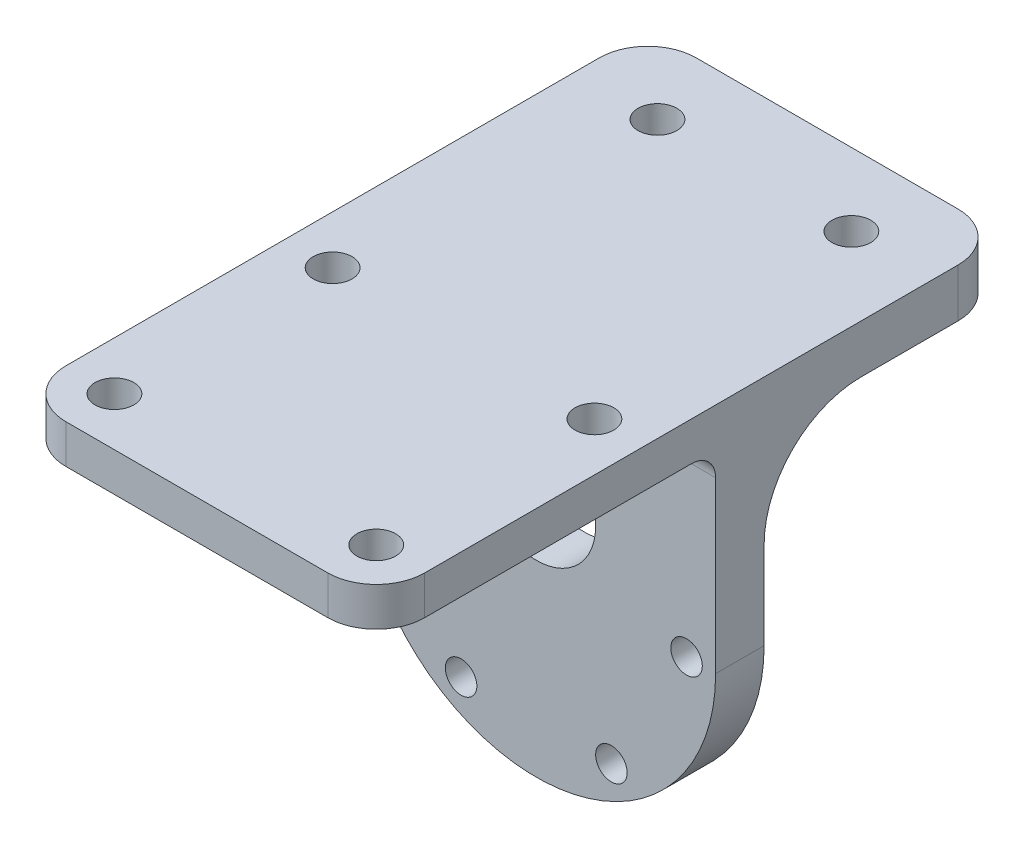
SolidWorks part; units mm, degrees
material "PMMA"
ref_plane "Front Plane" through (0, 0, 0) normal (0, 0, 1) x (1, 0, 0)
ref_plane "Top Plane" through (0, 0, 0) normal (0, 1, 0) x (1, 0, 0)
ref_plane "Right Plane" through (0, 0, 0) normal (1, 0, 0) x (0, 0, -1)
sketch "Sketch1" plane through (0, 0, 0) normal (0, 0, 1) x (1, 0, 0)
  line L0 (-18.5, 0) -> (18.5, 0) construction
  line L1 (0, 18.5) -> (0, -18.5) construction
  line L4 (-18.5, 0) -> (-18.5, 20)
  line L5 (-18.5, 20) -> (18.5, 20)
  line L6 (18.5, 0) -> (18.5, 20)
  arc A0 (-18.5, 0) -> (18.5, 0) centre (0, 0) ccw
  circle A1 centre (-15.5, 0) radius 1.625
  circle A2 centre (-7.75, 13.4234) radius 1.625 construction
  circle A3 centre (7.75, 13.4234) radius 1.625 construction
  circle A4 centre (15.5, 0) radius 1.625
  circle A5 centre (7.75, -13.4234) radius 1.625
  circle A6 centre (-7.75, -13.4234) radius 1.625
  circle A7 centre (0, 7) radius 6.125
  point P21 (0, 0)
  dimension "D1" = 37
  dimension "D2" = 3.25
  dimension "D6" = 12.25
  dimension "D3" = 15.5
  dimension "D5" = 7
  dimension "D7" = 15.5
  dimension "D8" = 20
  dimension "D4" = 6
extrude "Boss-Extrude2" add sketch "Sketch1" along normal blind 5 contours L4 A0 L6 L5 A7 A6 A5 A4 A3 A2 A1 region at (-17.966, 10, 0)
sketch "Sketch7" plane through (0, 0, 0) normal (0, 0, -1) x (-1, 0, 0)
  line L1 (-18.5, 20) -> (18.5, 20)
  line L2 (-18.5, 20) -> (-18.5, 24)
  line L3 (-18.5, 24) -> (18.5, 24)
  line L4 (18.5, 20) -> (18.5, 24)
  dimension "D1" = 4
extrude "Boss-Extrude7" add sketch "Sketch7" against normal blind 40
fillet "Fillet3" radius 2.5 1 edges at (0, 20, 5)
sketch "Sketch10" plane through (0, 0, 0) normal (0, 0, -1) x (-1, 0, 0)
  line L0 (18.5, 0) -> (18.5, 24) construction
  line L1 (-18.5, 24) -> (18.5, 24)
  line L2 (-18.5, 24) -> (-18.5, 19)
  line L3 (-18.5, 19) -> (18.5, 19)
  line L4 (18.5, 24) -> (18.5, 19)
  dimension "D1" = 5
extrude "Boss-Extrude8" add sketch "Sketch10" along normal blind 25
fillet "Fillet5" radius 5 4 edges at (-18.5, 21.5, -25) (-18.5, 22, 40) (18.5, 22, 40) (18.5, 21.5, -25)
hole_wizard "Ø4.0mm Dowel Hole1" positions "Sketch8" profile "Sketch9" hole size "Ø4.0" standard "ISO" end condition through all
sketch "Sketch8" plane through (0, 20, 0) normal (0, -1, 0) x (-1, 0, 0)
  line L0 (18.5, -35) -> (18.5, -7.5) construction
  line L1 (-13.5, -40) -> (13.5, -40) construction
  line L2 (18.5, -7.5) -> (-18.5, -7.5) construction
  line L3 (-18.5, -35) -> (-18.5, -7.5) construction
  point P0 (13.5, -35)
  point P2 (-13.5, -35)
  point P4 (-13.5, -12.5)
  point P6 (13.5, -12.5)
  dimension "D1" = 5
  dimension "D2" = 5
  dimension "D3" = 5
  dimension "D4" = 5
sketch "Sketch9" plane through (-13.5, 20, 35) normal (1, 0, 0) x (0, 0, -1)
  line L0 (0, 0) -> (0, 4)
  line L1 (0, 4) -> (2, 4)
  line L2 (2, 4) -> (2, 0)
  line L5 (2, 0) -> (0, 0)
  line L11 (0, -6.35) -> (0, 107.95) construction
  dimension "Thru Hole Dia." = 4
  dimension "Thru Hole Depth" = 4
fillet "Fillet6" radius 10 1 edges at (0, 19, 0)
hole_wizard "Ø4.0mm Dowel Hole3" positions "Sketch13" profile "Sketch14" hole size "Ø4.0" standard "ISO" end condition through all
sketch "Sketch13" plane through (0, 19, 0) normal (0, -1, 0) x (-1, 0, 0)
  line L1 (-10, 17.5) -> (10, 17.5) construction
  point P0 (-10, 17.5)
  point P2 (10, 17.5)
  point P16 (0, 17.5)
  dimension "D1" = 20
  dimension "D2" = 17.5
sketch "Sketch14" plane through (10, 19, -17.5) normal (1, 0, 0) x (0, 0, -1)
  line L0 (0, 0) -> (0, 5)
  line L1 (0, 5) -> (2, 5)
  line L2 (2, 5) -> (2, 0)
  line L5 (2, 0) -> (0, 0)
  line L11 (0, -6.35) -> (0, 107.95) construction
  dimension "Thru Hole Dia." = 4
  dimension "Thru Hole Depth" = 5
